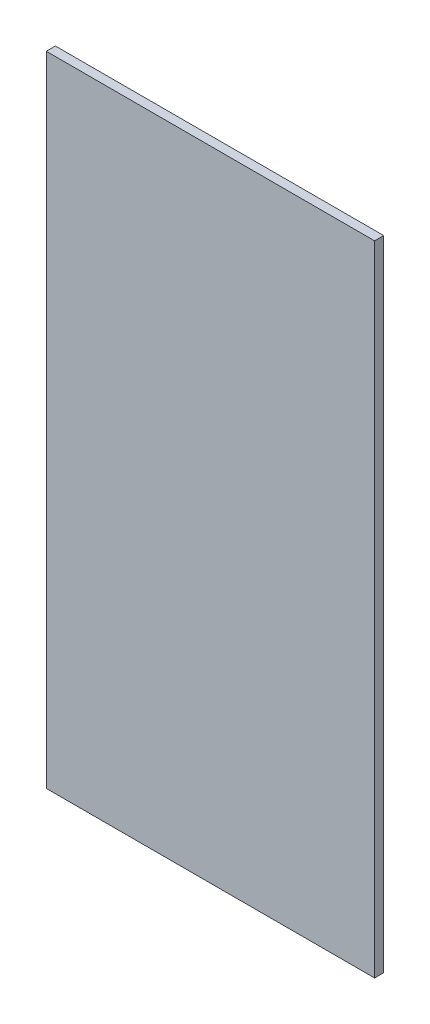
SolidWorks part; units mm, degrees
ref_plane "Front Plane" through (0, 0, 0) normal (0, 0, 1) x (1, 0, 0)
ref_plane "Top Plane" through (0, 0, 0) normal (0, 1, 0) x (1, 0, 0)
ref_plane "Right Plane" through (0, 0, 0) normal (1, 0, 0) x (0, 0, -1)
sketch "Sketch1" plane through (0, 0, 0) normal (0, 0, 1) x (1, 0, 0)
  line L1 (0, 0) -> (-228.6, 0)
  line L2 (0, 0) -> (0, -444.5)
  line L3 (0, -444.5) -> (-228.6, -444.5)
  line L4 (-228.6, 0) -> (-228.6, -444.5)
  dimension "D1" = 228.6
  dimension "D2" = 444.5
extrude "Boss-Extrude1" add sketch "Sketch1" along normal blind 6.35
ref_plane "Plane1" through (0, -444.5, 6.35) normal (1, 0, 0) x (0, 0, -1)
